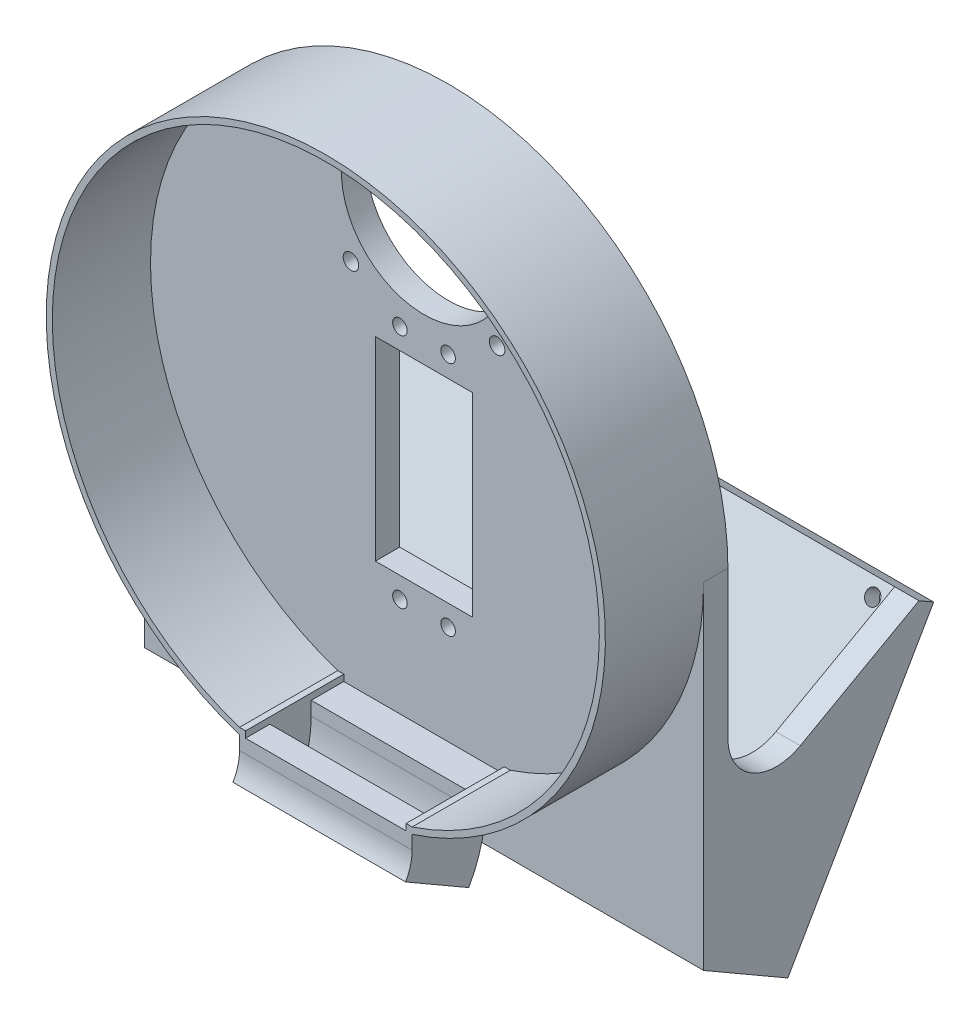
SolidWorks part; units mm, degrees
ref_plane "Front Plane" through (0, 0, 0) normal (0, 0, 1) x (1, 0, 0)
ref_plane "Top Plane" through (0, 0, 0) normal (0, 1, 0) x (1, 0, 0)
ref_plane "Right Plane" through (0, 0, 0) normal (1, 0, 0) x (0, 0, -1)
sketch "Sketch2" plane through (0, 0, 0) normal (0, 0, 1) x (1, 0, 0)
  line L0 (0, 0) -> (0, 10) construction
  line L1 (0, 10) -> (0, 35.9) construction
  line L2 (0, 0) -> (0, -10) construction
  line L3 (0, -10) -> (0, -57.5) construction
  line L4 (-54.6857, 17.7685) -> (-9.5106, 3.0902) construction
  line L5 (-9.5106, 3.0902) -> (0, 0) construction
  line L6 (0, 35.9) -> (0, 57.5) construction
  circle A0 centre (0, 0) radius 57.5
  point P7 (0, -33.75)
  point P11 (-32.0982, 10.4293)
  dimension "D1" = 115
  dimension "D2" = 20
  dimension "D3" = 72
  dimension "D4" = 21.6
extrude "Boss-Extrude1" add sketch "Sketch2" along normal blind 20.2
sketch "Sketch3" plane through (0, 0, 20.2) normal (0, 0, 1) x (1, 0, 0)
  circle A0 centre (0, 0) radius 56.25
  dimension "D1" = 112.5
extrude "Cut-Extrude1" cut sketch "Sketch3" against normal up to surface (20.2 mm away) up to face at (57.5, 0, 0)
sketch "Sketch5" plane through (0, 0, 0) normal (0, 0, -1) x (-1, 0, 0)
  line L0 (-57.5, 0) -> (57.5, 0) construction
  line L1 (-57.5, 0) -> (-57.5, -60.5)
  line L2 (-57.5, -60.5) -> (57.5, -60.5)
  line L3 (57.5, -60.5) -> (57.5, 0)
  arc A0 (57.5, 0) -> (-57.5, 0) centre (0, 0) ccw
  dimension "D1" = 60.5
extrude "Boss-Extrude2" add sketch "Sketch5" along normal blind 5
sketch "Sketch7" plane through (0, 0, 0) normal (0, 0, 1) x (1, 0, 0)
  line L0 (0, 10) -> (0, 0) construction
  line L1 (0, 0) -> (0, -30) construction
  line L2 (0, 10) -> (-10, 10)
  line L3 (-10, 10) -> (-10, -30)
  line L4 (-10, -30) -> (0, -30)
  line L5 (0, -30) -> (10, -30)
  line L6 (10, -30) -> (10, 10)
  line L7 (10, 10) -> (0, 10)
  line L8 (10, -30) -> (10, -34.3) construction
  line L9 (-10, -34.3) -> (-4.95, -34.3) construction
  line L10 (-10, -34.3) -> (-10, -30) construction
  line L11 (-4.95, -34.3) -> (4.95, -34.3) construction
  line L12 (-10, 10) -> (-10, 14.3) construction
  line L13 (4.95, -34.3) -> (10, -34.3) construction
  line L14 (10, 14.3) -> (10, 10) construction
  line L15 (-10, 14.3) -> (-4.95, 14.3) construction
  line L16 (0, 0) -> (0, 10) construction
  line L17 (0, 35.9) -> (0, 57.5) construction
  line L18 (15.026, 50.926) -> (0, 35.9) construction
  line L19 (0, 35.9) -> (-15.026, 20.874) construction
  line L20 (0, 35.9) -> (15.026, 20.874) construction
  line L21 (0, 35.9) -> (-15.026, 50.926) construction
  line L22 (-4.95, 14.3) -> (4.95, 14.3) construction
  line L23 (4.95, 14.3) -> (10, 14.3) construction
  circle A4 centre (-15.026, 50.926) radius 1.6
  circle A5 centre (0, 0) radius 56.25 construction
  circle A6 centre (0, 35.9) radius 17
  circle A7 centre (15.026, 20.874) radius 1.6
  circle A8 centre (15.026, 50.926) radius 1.6
  circle A9 centre (-15.026, 20.874) radius 1.6
  circle A10 centre (-4.95, -34.3) radius 1.5
  circle A11 centre (4.95, -34.3) radius 1.5
  circle A12 centre (4.95, 14.3) radius 1.5
  circle A13 centre (-4.95, 14.3) radius 1.5
  dimension "D7" = 34
  dimension "D10" = 3.2
  dimension "D11" = 3
  dimension "D2" = 40
  dimension "D3" = 20
  dimension "D4" = 48.6
  dimension "D6" = 10
  dimension "D5" = 9.9
  dimension "D12" = 34.3
  dimension "D9" = 45
  dimension "D8" = 42.5
extrude "Cut-Extrude3" cut sketch "Sketch7" against normal up to surface (5 mm away) up to face at (0, -15.875, -5)
sketch "Sketch24" plane through (0, 0, -5) normal (0, 0, -1) x (-1, 0, 0)
  line L0 (0, 0) -> (0, -57.5) construction
  line L1 (0, -57.5) -> (-17.75, -57.5)
  line L2 (-17.75, -57.5) -> (-17.75, -53.376)
  line L3 (0, -57.5) -> (17.75, -57.5)
  line L4 (17.75, -57.5) -> (17.75, -53.376)
  line L5 (-17.75, -53.376) -> (17.75, -53.376)
  arc A1 (-57.5, 0) -> (57.5, 0) centre (0, 0) ccw construction
  circle A2 centre (0, 0) radius 56.25 construction
  dimension "D1" = 35.5
extrude "Boss-Extrude3" add sketch "Sketch24" against normal up to surface (25.2 mm away) up to face at (56.25, 0, 20.2)
sketch "Sketch4" plane through (0, 0, 20.2) normal (0, 0, 1) x (1, 0, 0)
  line L0 (-16.5, -33.75) -> (-16.5, -57.5)
  line L1 (16.5, -33.75) -> (16.5, -57.5)
  line L3 (17.75, -57.5) -> (-17.75, -57.5) construction
  line L4 (-16.5, -57.5) -> (16.5, -57.5)
  arc A0 (16.5, -33.75) -> (-16.5, -33.75) centre (0, -33.75) ccw
  dimension "D1" = 33
extrude "Cut-Extrude2" cut sketch "Sketch4" against normal up to surface (20.2 mm away) up to face at (0, 1.437, 0)
sketch "Sketch27" plane through (-17.75, 0, 0) normal (-1, 0, 0) x (0, 0, 1)
  line L0 (20.2, -57.5) -> (30.2, -57.5) construction
  line L3 (30.2, -57.5) -> (21.5397, -62.5) construction
  line L5 (8.2, -57.5) -> (5.2, -57.5)
  line L6 (8.2, -57.5) -> (20.2, -57.5)
  line L7 (20.2, -57.5) -> (0, -57.5) construction
  line L8 (8.2, -57.5) -> (11.1474, -68.5) construction
  line L10 (8.5494, -70) -> (11.1474, -68.5)
  line L11 (11.1474, -68.5) -> (21.5397, -62.5)
  arc A2 (20.2, -57.5) -> (21.5397, -62.5) centre (30.2, -57.5) ccw
  arc A4 (5.2, -57.5) -> (8.5494, -70) centre (30.2, -57.5) ccw
  dimension "D1" = 30
  dimension "D2" = 10
  dimension "D3" = 12
  dimension "D4" = 3
extrude "Boss-Extrude4" add sketch "Sketch27" against normal up to surface (1.25 mm away) up to face at (-16.5, -55.438, 10.1)
sketch "Sketch29" plane through (-16.5, 0, 0) normal (1, 0, 0) x (0, 0, -1)
  line L3 (-8.5494, -70) -> (-9.8484, -69.25)
  line L8 (-20.2, -57.5) -> (-20.2, -54.6917)
  line L19 (-20.2, -57.5) -> (-15.2, -57.5) construction
  line L20 (-6.7, -57.5) -> (-5.2, -57.5) construction
  line L21 (-5.2, -57.5) -> (0, -57.5)
  line L22 (0, -57.5) -> (0, -54.6917)
  line L25 (-8.5494, -70) -> (-11.1474, -68.5) construction
  line L26 (-21.5397, -62.5) -> (-17.2096, -65)
  line L27 (-11.1474, -68.5) -> (-21.5397, -62.5) construction
  line L28 (-6.7, -57.5) -> (-6.7, -54.6917)
  line L29 (-20.2, -54.6917) -> (0, -54.6917) construction
  line L30 (-6.7, -54.6917) -> (0, -54.6917)
  line L31 (-15.2, -57.5) -> (-15.2, -54.6917)
  line L32 (-15.2, -54.6917) -> (-20.2, -54.6917)
  arc A4 (-8.5494, -70) -> (-5.2, -57.5) centre (-30.2, -57.5) ccw
  arc A6 (-21.5397, -62.5) -> (-20.2, -57.5) centre (-30.2, -57.5) ccw
  arc A8 (-17.2096, -65) -> (-15.2, -57.5) centre (-30.2, -57.5) ccw
  arc A9 (-9.8484, -69.25) -> (-6.7, -57.5) centre (-30.2, -57.5) ccw
  dimension "D1" = 1.5
  dimension "D2" = 5
extrude "Boss-Extrude7" add sketch "Sketch29" along normal up to surface (33 mm away) up to face at (16.5, -55.438, 10.1)
sketch "Sketch30" plane through (16.5, 0, 0) normal (1, 0, 0) x (0, 0, -1)
  line L0 (-21.5397, -62.5) -> (-8.5494, -70)
  line L1 (-20.2, -57.5) -> (-5.2, -57.5)
  arc A0 (-8.5494, -70) -> (-5.2, -57.5) centre (-30.2, -57.5) ccw
  arc A1 (-21.5397, -62.5) -> (-20.2, -57.5) centre (-30.2, -57.5) ccw
extrude "Boss-Extrude8" add sketch "Sketch30" along normal up to surface (1.25 mm away) up to face at (17.75, -56.0959, 10.1)
sketch "Sketch31" plane through (-57.5, 0, 0) normal (-1, 0, 0) x (0, 0, 1)
  line L0 (-5, -60.5) -> (0, -60.5)
  line L1 (0, -60.5) -> (0, -69.1603)
  line L3 (-5, -60.5) -> (0, -69.1603) construction
  line L5 (-22.3205, -70.5) -> (-17.3205, -79.1603)
  line L6 (-17.3205, -79.1603) -> (0, -69.1603)
  line L7 (-22.3205, -70.5) -> (-47.3205, -27.1987)
  line L8 (-47.3205, -27.1987) -> (-44.2894, -25.4487)
  line L9 (-44.2894, -25.4487) -> (-19.2894, -68.75)
  line L10 (-22.3205, -70.5) -> (-19.2894, -68.75) construction
  line L11 (-5, -60.5) -> (-19.2894, -68.75)
  dimension "D2" = 20
  dimension "D1" = 60
  dimension "D3" = 3.5
  dimension "D4" = 50
extrude "Boss-Extrude9" add sketch "Sketch31" against normal up to surface (115 mm away) up to face at (57.5, -30.25, -2.5)
sketch "Sketch33" plane through (-57.5, 0, 0) normal (-1, 0, 0) x (0, 0, 1)
  line L0 (-5, -60.5) -> (-5, 0) construction
  line L2 (-5, -47.3762) -> (-44.2894, -25.4487)
  line L3 (-44.2894, -25.4487) -> (-19.2894, -68.75)
  line L4 (-19.2894, -68.75) -> (-5, -60.5)
  line L5 (-5, -60.5) -> (-5, -47.3762)
  line L6 (-5, -47.3762) -> (0, -56.0365) construction
  line L7 (0, -57.5) -> (0, -54.6917) construction
  line L8 (0, -54.6917) -> (0, 0) construction
  dimension "D1" = 30
extrude "Boss-Extrude10" add sketch "Sketch33" against normal blind 5
fillet "Fillet1" radius 10 1 edges at (-55, -47.3762, -5)
mirror "Mirror1" about plane through (0, 0, 0) normal (1, 0, 0) of "Fillet1", "Boss-Extrude10"
sketch "Sketch34" plane through (0, 0, 0) normal (1, 0, 0) x (0, 0, -1)
  line L0 (5, -60.5) -> (7.515, -56.1438) construction
  line L1 (5, -30.3432) -> (5, -42.5175) construction
  line L2 (7.515, -56.1438) -> (21.8045, -64.3938) construction
  line L3 (44.2894, -25.4487) -> (19.2894, -68.75) construction
  line L4 (5, -60.5) -> (19.2894, -68.75)
  line L5 (0, -54.6917) -> (5, -54.6917) construction
  line L6 (19.2894, -68.75) -> (5, -60.5) construction
  line L7 (5, -60.5) -> (5, -30.3432) construction
  line L8 (5, -54.6917) -> (7.515, -56.1438) construction
  line L9 (5, -60.5) -> (5, -54.6917)
  line L10 (5, -54.6917) -> (30.0545, -50.1044)
  line L11 (30.0545, -50.1044) -> (21.8045, -64.3938)
  line L12 (19.2894, -68.75) -> (21.8045, -64.3938)
  line L13 (19.8734, -39.0753) -> (5, -42.5175) construction
  line L14 (5, -42.5175) -> (5, -54.6917) construction
extrude "Boss-Extrude11" add sketch "Sketch34" along normal mid plane 5
fillet "Fillet2" radius 5 2 edges at (0, -54.6917, -5) (0, -50.1044, -30.0545)
sketch "Sketch37" plane through (0, -27.2901, -47.2678) normal (0, -0.5, -0.866) x (-1, 0, 0)
  line L0 (-52.5, 0.1055) -> (-52.5, -5.8945) construction
  line L2 (-52.5, 0.1055) -> (-52.5, -49.8945) construction
  line L4 (-52.5, -5.8945) -> (-46.5, 0.1055) construction
  line L5 (-57.5, 0.1055) -> (57.5, 0.1055) construction
  line L6 (-46.5, 0.1055) -> (-52.5, 0.1055) construction
  line L7 (52.5, 0.1055) -> (52.5, -5.8945) construction
  line L8 (52.5, 0.1055) -> (52.5, -49.8945) construction
  line L9 (52.5, -5.8945) -> (46.5, 0.1055) construction
  line L10 (46.5, 0.1055) -> (52.5, 0.1055) construction
  line L11 (-52.5, -49.8945) -> (-52.5, -43.8945) construction
  line L12 (-52.5, -43.8945) -> (-46.5, -49.8945) construction
  line L13 (-46.5, -49.8945) -> (-52.5, -49.8945) construction
  line L14 (52.5, -49.8945) -> (52.5, -43.8945) construction
  line L15 (52.5, -43.8945) -> (46.5, -49.8945) construction
  line L16 (46.5, -49.8945) -> (52.5, -49.8945) construction
  line L22 (-2.5, -49.8945) -> (-8.5, -49.8945) construction
  line L23 (-52.5, -49.8945) -> (-2.5, -49.8945) construction
  line L24 (-8.5, -49.8945) -> (-2.5, -43.8945) construction
  line L25 (-2.5, -49.8945) -> (-2.5, -26.0528) construction
  line L26 (-2.5, -43.8945) -> (-2.5, -49.8945) construction
  line L27 (2.5, -49.8945) -> (2.5, -43.8945) construction
  line L28 (2.5, -49.8945) -> (2.5, -26.0528) construction
  line L29 (2.5, -43.8945) -> (8.5, -49.8945) construction
  line L30 (2.5, -49.8945) -> (52.5, -49.8945) construction
  line L31 (8.5, -49.8945) -> (2.5, -49.8945) construction
  line L32 (2.5, -43.8945) -> (2.5, -5.8945) construction
  line L33 (2.5, -5.8945) -> (8.5, 0.1055) construction
  line L34 (8.5, 0.1055) -> (2.5, 0.1055) construction
  line L35 (2.5, 0.1055) -> (2.5, -5.8945) construction
  line L36 (-3.5, -5.8945) -> (2.5, -5.8945) construction
  line L37 (-3.5, -5.8945) -> (-3.5, 0.1055) construction
  line L38 (-3.5, 0.1055) -> (-9.5, 0.1055) construction
  line L39 (-9.5, 0.1055) -> (-3.5, -5.8945) construction
  circle A0 centre (-49.5, -2.8945) radius 1.5
  circle A1 centre (49.5, -2.8945) radius 1.5
  circle A2 centre (49.5, -46.8945) radius 1.5
  circle A3 centre (-49.5, -46.8945) radius 1.5
  circle A4 centre (5.5, -2.8945) radius 1.5
  circle A5 centre (-6.5, -2.8945) radius 1.5
  circle A6 centre (5.5, -46.8945) radius 1.5
  circle A7 centre (-5.5, -46.8945) radius 1.5
  dimension "D2" = 3
  dimension "D1" = 6
extrude "Cut-Extrude6" cut sketch "Sketch37" against normal up to surface (3.5 mm away) up to face at (0, -52.7628, -28.5196)
equation "\"board_length\"= 260mm"
equation "\"board_height\"= 200mm"
equation "\"board_width\"= 16.5mm"
equation "\"token_thickness\"= 7mm"
equation "\"token_diameter\"= 32mm"
equation "\"board_side_lower_height\"= 55mm"
equation "\"board_side_height\"= 156.5mm"
equation "\"board_side_length\"= 100mm"
equation "\"board_slot_width\"= \"board_length\" / 7"
equation "\"token_ridge\"= ( \"token_thickness\" - 4mm ) / 2"
equation "\"token_ridge_width\"= 1.5mm"
equation "\"25T_outer_diameter\"= 20mm"
equation "\"25T_inner_diameter\"= 9mm"
equation "\"2T_screw_distance\" = 14mm"
equation "\"2T_outer_thickness\"= 2mm"
equation "\"2T_inner_thickness\"= 4.5mm"
equation "\"MG996R_outer_length\"= 54mm"
equation "\"MG996R_inner_length\"= 40mm"
equation "\"MG996R_width\"= 20mm"
equation "\"MG996R_height\" = 26.6mm"
equation "\"MG996R_full_height\"= 45.7mm"
equation "\"MG996R_full_width\"= 55.5mm"
equation "\"MG996R_screw_distance\"= 10mm"
equation "\"magnet_diameter\" = 10mm"
equation "\"magnet_thickness\"= 2mm"
equation "\"dispenser_barrel_margin\"= 2.5mm"
equation "\"dispenser_wheel_width\"= \"token_thickness\" + 5mm"
equation "\"D1@Sketch2\"=\"MG996R_outer_length\"*2+\"dispenser_cover_margin\"+4mm"
equation "\"dispenser_cover_margin\"= 3.0mm"
equation "\"D1@Boss-Extrude1\"=\"MG996R_full_height\"-\"MG996R_mid_height\"+\"dispenser_wheel_width\""
equation "\"D1@Sketch3\"=\"MG996R_outer_length\"*2+4.5mm"
equation "\"D2@Sketch2\"=\"25T_outer_diameter\""
equation "\"D1@Sketch4\"=\"token_diameter\"+1.0mm"
equation "\"dispenser_cover_thickness\"= 5.0mm"
equation "\"D1@Boss-Extrude2\"=\"dispenser_cover_thickness\""
equation "\"D1@Sketch5\"=\"dispenser_cover_margin\"/2+\"MG996R_outer_length\"+5.0mm"
equation "\"MG996R_major_axis_distance\"= 34.3mm"
equation "\"D2@Sketch7\"=\"MG996R_inner_length\""
equation "\"D3@Sketch7\"=\"MG996R_width\""
equation "\"D4@Sketch7\"=\"MG996R_major_screw_distance\""
equation "\"D6@Sketch7\"=\"25T_outer_diameter\"/2"
equation "\"D7@Sketch7\"=\"token_diameter\"+2.0mm"
equation "\"MG996R_major_screw_distance\"= 48.6mm"
equation "\"MG996R_minor_screw_distance\"= 9.9mm"
equation "\"D5@Sketch7\"=\"MG996R_minor_screw_distance\""
equation "\"D12@Sketch7\"=\"MG996R_major_axis_distance\""
equation "\"MG996R_mid_height\"= 37.5mm"
equation "\"D1@Sketch24\"=\"token_diameter\"+\"dispenser_cover_margin\"+0.5mm"
equation "\"dispenser_slope\"= 30deg"
equation "\"D1@Sketch27\"=\"dispenser_slope\""
equation "\"D2@Sketch27\"=\"dispenser_cover_thickness\"*2"
equation "\"D3@Sketch27\"=\"dispenser_wheel_width\""
equation "\"D4@Sketch27\"=\"dispenser_cover_margin\""
equation "\"D1@Sketch29\"=\"dispenser_cover_margin\"/2"
equation "\"D2@Sketch29\"=\"dispenser_wheel_width\"-\"token_thickness\""
equation "\"D1@Sketch31\"=90-\"dispenser_slope\""
equation "\"D4@Sketch2\"=\"token_diameter\"/2*1.35"
equation "\"dispenser_cover_length\"= 20mm"
equation "\"D2@Sketch31\"=\"dispenser_cover_length\""
equation "\"dispenser_carrier_width\" = 3.5mm"
equation "\"dispenser_carrier_height\"= 50mm"
equation "\"D4@Sketch31\"=\"dispenser_carrier_height\""
equation "\"D3@Sketch31\"=\"dispenser_carrier_width\""
equation "\"D1@Boss-Extrude10\"=\"dispenser_cover_thickness\""
equation "\"D1@Fillet1\"=\"dispenser_cover_length\"/2"
equation "\"D1@Sketch33\"=\"dispenser_slope\""
equation "\"D1@Boss-Extrude11\"=\"dispenser_cover_thickness\""
equation "\"D1@Fillet2\"=\"dispenser_cover_thickness\""
equation "\"D8@Sketch7\"=\"token_diameter\"+\"dispenser_barrel_margin\"+8.0mm"
